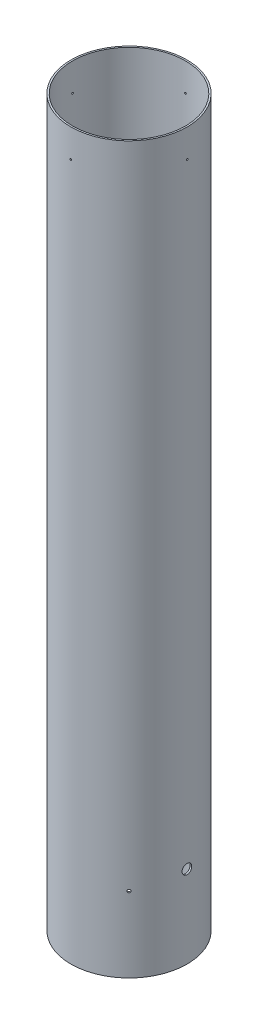
SolidWorks part; units mm, degrees
material "A-Glass Fiber"
ref_plane "Front Plane" through (0, 0, 0) normal (0, 0, 1) x (1, 0, 0)
ref_plane "Top Plane" through (0, 0, 0) normal (0, 1, 0) x (1, 0, 0)
ref_plane "Right Plane" through (0, 0, 0) normal (1, 0, 0) x (0, 0, -1)
sketch "Sketch1" plane through (0, 0, 0) normal (0, 1, 0) x (1, 0, 0)
  circle A0 centre (0, 0) radius 76.1746
  circle A1 centre (0, 0) radius 78.359
  dimension "D1" = 156.718
  dimension "D2" = 152.3492
extrude "Boss-Extrude1" add sketch "Sketch1" along normal blind 977.9
ref_axis "Axis1" through (0, 977.9, 0) along (0, -1, 0)
sketch "Sketch2" plane through (0, 0, 0) normal (1, 0, 0) x (0, 0, -1)
  line L0 (78.359, 977.9) -> (-78.359, 977.9) construction
  circle A0 centre (0, 939.8) radius 1.0922
  dimension "D1" = 2.1844
  dimension "D2" = 38.1
extrude "Cut-Extrude1" cut sketch "Sketch2" against normal through all
pattern_circular "CirPattern1" count 4 over 360 about axis through (0, 977.9, 0) along (0, 1, 0) of "Cut-Extrude1"
ref_plane "Plane1" through (0, 0, 0) normal (0.7071, 0, 0.7071) x (0, -1, 0)
hole_wizard "1/2 Clearance Hole1" positions "Sketch3" profile "Sketch4" hole size "1/2" standard "ANSI Inch"
sketch "Sketch3" plane through (0, 0, 0) normal (1, 0, 0) x (0, 0, -1)
  point P0 (0, 111.125)
  dimension "D1" = 111.125
sketch "Sketch4" plane through (0, 111.125, 0) normal (0, 1, 0) x (0, 0, 1)
  line L0 (0, 0) -> (0, 92.8345)
  line L1 (0, 92.8345) -> (6.5481, 88.9)
  line L2 (6.5481, 88.9) -> (6.5481, 0)
  line L5 (6.5481, 0) -> (0, 0)
  line L10 (0, 92.8345) -> (-6.5481, 88.9) construction
  line L11 (0, -6.35) -> (0, 107.95) construction
  dimension "Hole Dia." = 13.0962
  dimension "Hole Depth" = 88.9
  dimension "Drill Angle" = 118
hole_wizard "Ø4.0 (4) Diameter Hole1" positions "Sketch5" profile "Sketch6" hole size "Ø4.0" standard "ANSI Metric"
sketch "Sketch5" plane through (0, 0, 0) normal (0.7071, 0, 0.7071) x (0.7071, 0, -0.7071)
  point P0 (0, 101.6)
  dimension "D1" = 101.6
sketch "Sketch6" plane through (0, 101.6, 0) normal (0, 1, 0) x (0.7071, 0, -0.7071)
  line L0 (0, 0) -> (0, 90.1017)
  line L1 (0, 90.1017) -> (2, 88.9)
  line L2 (2, 88.9) -> (2, 0)
  line L5 (2, 0) -> (0, 0)
  line L10 (0, 90.1017) -> (-2, 88.9) construction
  line L11 (0, -6.35) -> (0, 107.95) construction
  dimension "Hole Dia." = 4
  dimension "Hole Depth" = 88.9
  dimension "Drill Angle" = 118
pattern_circular "CirPattern2" count 4 over 360 about axis through (0, 0, 0) along (0, 1, 0) of "Ø4.0 (4) Diameter Hole1"
equation "\"Fwd_Tube_Length\" = 38.5in"
equation "\"D1@Boss-Extrude1\" = \"Fwd_Tube_Length\""
equation "\"BKHD_Screw_Diam\"= 3.5mm"
equation "\"Fwd_BKHD_From_Top\" = 18in"
equation "\"Bodytube_OD\" = 6.17in"
equation "\"Bodytube_ID\" = 5.998in"
equation "\"D2@Sketch1\"=\"Bodytube_ID\""
equation "\"D1@Sketch1\"=\"Bodytube_OD\""
equation "\"Shear_Screw_Diameter\" = 0.086in"
equation "\"Shear_Screw_Coupler_Location\" = 4.5in"
equation "\"Motor_OD\" = 4in"
equation "\"Mid_Tube_Length\"= 1in"
equation "\"Mid_Coupler_Length\" = 13in"
equation "\"Aft_Section_Length\"= 36in"
equation "\"AB_Coupler_OD_Length\"= 1in"
equation "\"AB_Coupling_Section_Length\"= 0.375in"
equation "\"AB_Coupler_Length\"= \"AB_Coupler_OD_Length\" + \"AB_Coupling_Section_Length\" * 2"
equation "\"Cutout_Angle\" = 80"
equation "\"AB_Paddle_Height\" = 0.375in"
equation "\"AB_Coupler_Num_Screws\"= 4"
equation "\"AB_BKHD_Thickness\" = 0.375in"
equation "\"AB_Mount_From_Bottom\" = 23.175in"
equation "\"Num_Cutouts\" = 3"
equation "\"AB_Coupler_OD\"= 6.17in"
equation "\"AB_Coupler_ID\"= 5.75in"
equation "\"AB_Coupler_Surface_Diameter\"= 5.998in"
equation "\"AB_Coupling_Screw_Diameter\"= 0.15748in"
equation "\"AB_Central_Bushing_Length\" = .4724in"
equation "\"Lead_Screw_Dist\" = 3.4in"
equation "\"Lead_Screw_Diam\" = 0.386in"
equation "\"Lead_Screw_Length\" = (\"Mid_Coupler_Length\" + 2*0.375in + 2*.75in)"
equation "\"Paddle_Pin_Offset\" = .25in"
equation "\"Paddle_Pin_Radius\" = 2.25in"
equation "\"SS_Paddle_Pin_Radius\" = 2.25*0.66in"
equation "\"Paddle_Gear_OD\" = 3.2in"
equation "\"Drive_Gear_OD\" = 1.7in"
equation "\"Fin_Thickness\"= .118in"
equation "\"Guiderail_Cutout_Diameter\"= 1.5in"
equation "\"DB9_Hole_Dist\" = 25mm"
equation "\"DB9_Relief_Width\" = 0.47in"
equation "\"DB9_Relief_Hole_Offset\" = 0.09in"
equation "\"Airbrakes_Wire_Hole_Dia\" = .25in"
equation "\"Airbrakes_Wire_Hole_Dist\" = 1.1in"
equation "\"Servo_Gear_Offset\" = 0.5in"
equation "\"D1@Sketch2\"=\"Shear_Screw_Diameter\""
equation "\"FWD_Shear_Screw_Dist\" = 1.5in"
equation "\"D2@Sketch2\"=\"FWD_Shear_Screw_Dist\""
